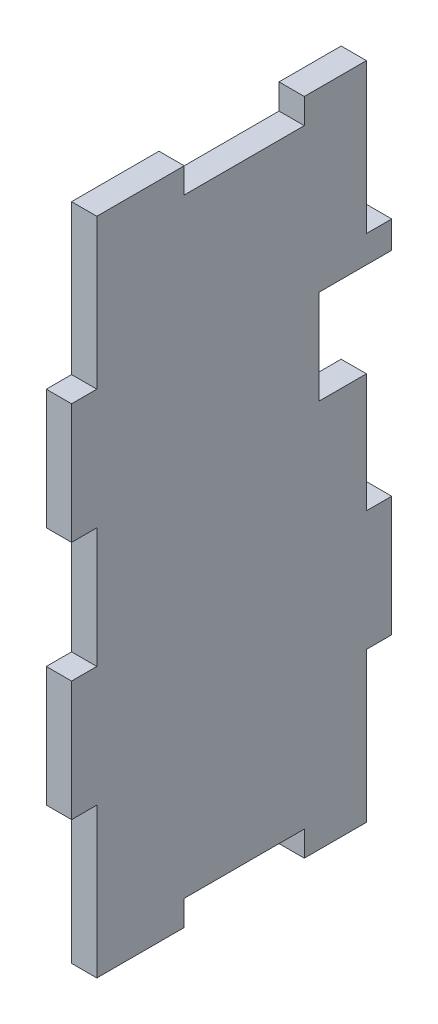
SolidWorks part; units mm, degrees
ref_plane "Front Plane" through (0, 0, 0) normal (0, 0, 1) x (1, 0, 0)
ref_plane "Top Plane" through (0, 0, 0) normal (0, 1, 0) x (1, 0, 0)
ref_plane "Right Plane" through (0, 0, 0) normal (1, 0, 0) x (0, 0, -1)
sketch "Sketch1" plane through (0, 0, 0) normal (1, 0, 0) x (0, 0, -1)
  line L122 (-18.5579, 36.9831) -> (-18.5579, 19.2081)
  line L123 (-18.5579, 19.2081) -> (-21.5579, 19.2081)
  line L124 (-21.5579, 19.2081) -> (-21.5579, 4.9581)
  line L125 (-21.5579, 4.9581) -> (-18.5579, 4.9581)
  line L126 (-18.5579, 4.9581) -> (-18.5579, -9.2919)
  line L127 (-18.5579, -9.2919) -> (-21.5579, -9.2919)
  line L128 (-21.5579, -9.2919) -> (-21.5579, -23.5419)
  line L129 (-21.5579, -23.5419) -> (-18.5579, -23.5419)
  line L130 (-18.5579, -23.5419) -> (-18.5579, -37.7919)
  line L131 (-18.5579, -37.7919) -> (-18.5579, -41.3169)
  line L132 (-18.5579, -41.3169) -> (-8.1829, -41.3169)
  line L133 (-8.1829, -41.3169) -> (-8.1829, -38.3169)
  line L134 (-8.1829, -38.3169) -> (6.0671, -38.3169)
  line L135 (6.0671, -38.3169) -> (6.0671, -41.3169)
  line L136 (6.0671, -41.3169) -> (13.4421, -41.3169)
  line L137 (13.4421, -41.3169) -> (13.4421, -23.5419)
  line L138 (13.4421, -23.5419) -> (16.4421, -23.5419)
  line L139 (16.4421, -23.5419) -> (16.4421, -9.2919)
  line L140 (16.4421, -9.2919) -> (13.4421, -9.2919)
  line L141 (13.4421, -9.2919) -> (13.4421, 4.9581)
  line L142 (13.4421, 4.9581) -> (16.4421, 4.9581)
  line L143 (16.4421, 4.9581) -> (16.4421, 19.2081)
  line L144 (16.4421, 19.2081) -> (13.4421, 19.2081)
  line L145 (13.4421, 19.2081) -> (13.4421, 33.4581)
  line L146 (13.4421, 33.4581) -> (13.4421, 36.9831)
  line L147 (13.4421, 36.9831) -> (6.0671, 36.9831)
  line L148 (6.0671, 36.9831) -> (6.0671, 33.9831)
  line L149 (6.0671, 33.9831) -> (-8.1829, 33.9831)
  line L150 (-8.1829, 33.9831) -> (-8.1829, 36.9831)
  line L151 (-8.1829, 36.9831) -> (-18.5579, 36.9831)
  dimension "D1" = 7.375
extrude "Boss-Extrude1" add sketch "Sketch1" along normal blind 3
sketch "Sketch2" plane through (3, 0, 0) normal (1, 0, 0) x (0, 0, -1)
  line L0 (13.4421, 36.9831) -> (6.0671, 36.9831) construction
  line L1 (7.8144, 15.9831) -> (17.8144, 15.9831)
  line L2 (7.8144, 15.9831) -> (7.8144, 4.791)
  line L3 (7.8144, 4.791) -> (17.8144, 4.791)
  line L4 (17.8144, 15.9831) -> (17.8144, 4.791)
  dimension "D1" = 21
  dimension "D2" = 10
extrude "Cut-Extrude1" cut sketch "Sketch2" against normal blind 10
